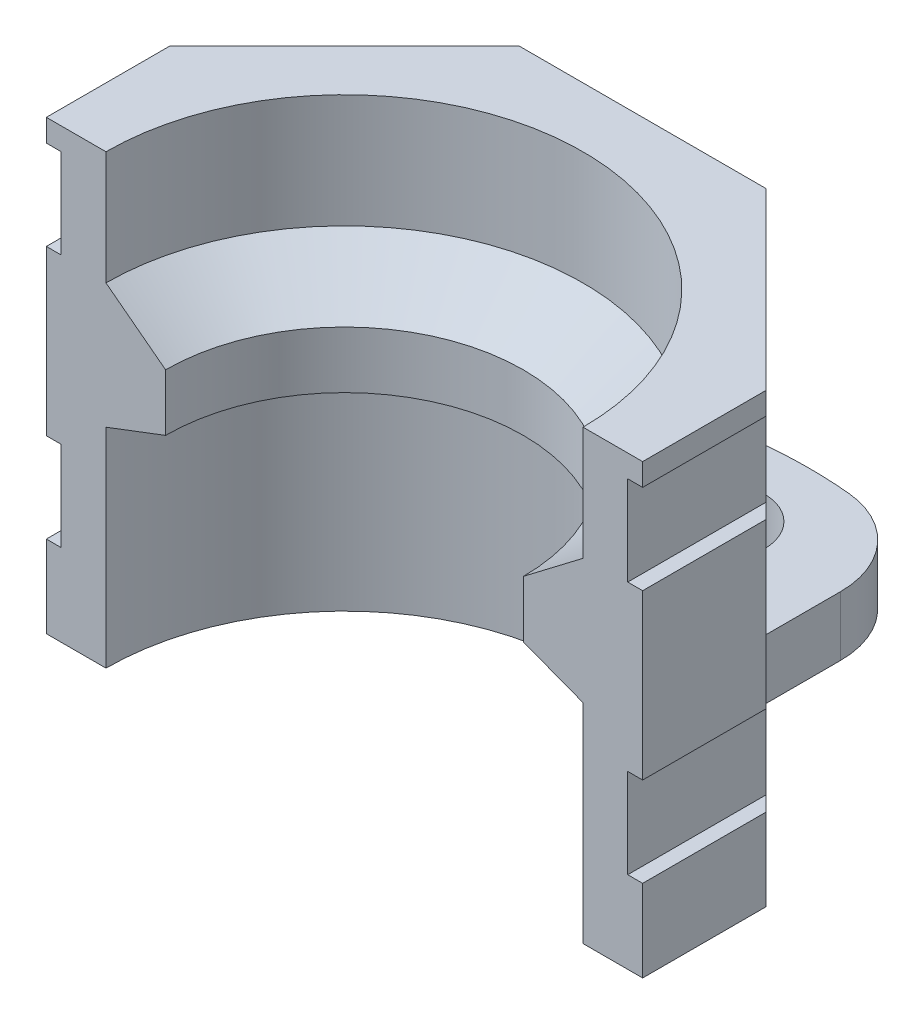
SolidWorks part; units mm, degrees
ref_plane "Front Plane" through (0, 0, 0) normal (0, 0, 1) x (1, 0, 0)
ref_plane "Top Plane" through (0, 0, 0) normal (0, 1, 0) x (1, 0, 0)
ref_plane "Right Plane" through (0, 0, 0) normal (1, 0, 0) x (0, 0, -1)
sketch "Sketch2" plane through (0, 0, 0) normal (0, 1, 0) x (1, 0, 0)
  line L0 (0, 10) -> (0, 0) construction
  line L1 (0, 0) -> (10, 0) construction
  line L2 (4.1421, 10) -> (-4.1421, 10)
  line L3 (-4.1421, 10) -> (-10, 4.1421)
  line L4 (-10, 4.1421) -> (-10, -4.1421)
  line L5 (4.1421, 10) -> (10, 4.1421)
  line L6 (10, 4.1421) -> (10, -4.1421)
  line L7 (4.1421, -10) -> (10, -4.1421)
  line L8 (4.1421, -10) -> (-4.1421, -10)
  line L9 (-4.1421, -10) -> (-10, -4.1421)
  point P9 (0, 10)
  point P12 (10, 0)
  point P15 (-10, 0)
  dimension "D1" = 20
extrude "Boss-Extrude1" add sketch "Sketch2" along normal blind 20
sketch "Sketch4" plane through (0, 0, 0) normal (0, 0, 1) x (1, 0, 0)
  line L0 (0, -24.1617) -> (0, 0) construction
  line L1 (-4.1421, 0) -> (4.1421, 0) construction
  line L2 (0, 0) -> (0, 20)
  line L4 (0, 20) -> (-4.625, 20)
  line L5 (-4.625, 20) -> (-4.375, 17)
  line L6 (-4.375, 17) -> (-1, 17)
  line L7 (-1, 17) -> (-1, 15)
  line L8 (-1, 15) -> (-8, 15)
  line L9 (-8, 15) -> (-8, 11.19)
  line L10 (-8, 11.19) -> (-6, 9.666)
  line L11 (-6, 9.666) -> (-6, 7.761)
  line L12 (-6, 7.761) -> (-8, 6.999)
  line L13 (-8, 6.999) -> (-8, 0)
  line L14 (-8, 0) -> (0, 0)
  line L15 (-4.1421, 20) -> (4.1421, 20) construction
  dimension "D1" = 2
  dimension "D2" = 9.25
  dimension "D3" = 8.75
  dimension "D4" = 3
  dimension "D5" = 3.81
  dimension "D6" = 1.524
  dimension "D7" = 16
  dimension "D8" = 12
  dimension "D9" = 4.191
  dimension "D10" = 1.905
  dimension "D11" = 2
revolve "Cut-Revolve3" cut sketch "Sketch4" angle 360 about L0
chamfer "Chamfer2" distance 3 angle 45 8 edges at (7.0711, 20, 7.0711) (0, 20, 10) (-7.0711, 20, 7.0711) (-10, 20, 0) (-7.0711, 20, -7.0711) (0, 20, -10) (7.0711, 20, -7.0711) (10, 20, 0)
sketch "Sketch7" plane through (0, 0, 0) normal (0, 0, 1) x (1, 0, 0)
  line L0 (-10, 8.5) -> (10, 8.5) construction
  line L1 (-10, 17) -> (-10, 0) construction
  line L2 (10, 17) -> (10, 0) construction
  line L3 (0, 0) -> (0, 17) construction
  line L4 (4.1421, 17) -> (-4.1421, 17) construction
  line L5 (-10, 2.75) -> (-9.5, 2.75)
  line L6 (-10, 14.25) -> (-9.5, 14.25)
  line L7 (-10, 14.25) -> (-10, 11.25)
  line L8 (-10, 11.25) -> (-9.5, 11.25)
  line L9 (-9.5, 14.25) -> (-9.5, 11.25)
  line L10 (-10, 2.75) -> (-10, 5.75)
  line L11 (-10, 5.75) -> (-9.5, 5.75)
  line L12 (-9.5, 2.75) -> (-9.5, 5.75)
  line L13 (10, 2.75) -> (9.5, 2.75)
  line L14 (9.5, 2.75) -> (9.5, 5.75)
  line L15 (10, 2.75) -> (10, 5.75)
  line L16 (10, 5.75) -> (9.5, 5.75)
  line L17 (10, 14.25) -> (9.5, 14.25)
  line L18 (10, 14.25) -> (10, 11.25)
  line L19 (10, 11.25) -> (9.5, 11.25)
  line L20 (9.5, 14.25) -> (9.5, 11.25)
  line L21 (-9.5, 11.25) -> (-9.5, 8.5) construction
  line L22 (-9.5, 17) -> (-9.5, 14.25) construction
  line L23 (-4.1421, 17) -> (-10, 17) construction
  dimension "D1" = 3
  dimension "D2" = 0.5
extrude "Cut-Extrude5" cut sketch "Sketch7" against normal through all both and the other way through all
sketch "Sketch8" plane through (0, 0, 0) normal (0, 1, 0) x (1, 0, 0)
  line L0 (0, 0) -> (10.8137, 6.27) construction
  line L1 (-4.1421, 10) -> (-4.1421, 12.5481)
  line L2 (-0.0231, 12.5) -> (-0.0231, 17.238) construction
  line L3 (-0.0231, 12.5) -> (-0.0231, 14.1) construction
  line L4 (-4.1421, 10) -> (0, 10)
  line L5 (-4.1421, 10) -> (4.1421, 10) construction
  line L6 (4.0959, 10) -> (4.0959, 12.5481)
  line L7 (4.0959, 10) -> (-0.0463, 10)
  line L8 (-4.1421, -10) -> (-10.1285, -10)
  line L9 (-12.6282, -8.6588) -> (-13.1321, -7.8995)
  line L10 (-12.379, -3.8017) -> (-11.2534, -2.9956)
  line L11 (-10, -0.5565) -> (-10, -4.1421)
  line L12 (-10, -4.1421) -> (-10, 4.1421) construction
  line L13 (-10, -4.1421) -> (-4.1421, -10)
  line L14 (9.9537, -4.1421) -> (4.0959, -10)
  line L15 (9.9537, -0.5565) -> (9.9537, -4.1421)
  line L16 (12.3327, -3.8017) -> (11.2071, -2.9956)
  line L17 (12.582, -8.6588) -> (13.0858, -7.8995)
  line L18 (4.0959, -10) -> (10.0823, -10)
  circle A0 centre (10.8137, 6.27) radius 1.6 construction
  circle A1 centre (10.8369, -6.23) radius 1.6
  circle A2 centre (0.0231, -12.5) radius 1.6 construction
  circle A3 centre (-10.8137, -6.27) radius 1.6
  circle A4 centre (-10.8369, 6.23) radius 1.6 construction
  circle A5 centre (-0.0231, 12.5) radius 1.6
  arc A6 (-1.4141, 15.5358) -> (-0.0231, 15.6) centre (0, 0) cw
  arc A7 (1.3678, 15.5358) -> (-0.0231, 15.6) centre (-0.0463, 0) ccw
  arc A8 (1.3678, 15.5358) -> (4.0959, 12.5481) centre (1.0959, 12.5481) cw
  arc A9 (-4.1421, 12.5481) -> (-1.4141, 15.5358) centre (-1.1421, 12.5481) cw
  arc A10 (-13.1321, -7.8995) -> (-12.379, -3.8017) centre (-10.6324, -6.2408) cw
  arc A11 (-10.1285, -10) -> (-12.6282, -8.6588) centre (-10.1285, -7) cw
  arc A12 (-11.2534, -2.9956) -> (-10, -0.5565) centre (-13, -0.5565) ccw
  arc A13 (11.2071, -2.9956) -> (9.9537, -0.5565) centre (12.9537, -0.5565) cw
  arc A14 (13.0858, -7.8995) -> (12.3327, -3.8017) centre (10.5861, -6.2408) ccw
  arc A15 (10.0823, -10) -> (12.582, -8.6588) centre (10.0823, -7) ccw
  point P29 (4.0959, 15.04)
  point P32 (-4.1421, 15.04)
  point P43 (-10, -2.0981)
  point P49 (-14.7328, -5.4872)
  point P52 (-11.7382, -10)
  dimension "D3" = 3.2
  dimension "D5" = 3
  dimension "D6" = 3
  dimension "D7" = 3
  dimension "D8" = 3
  dimension "D2" = 12.5
  dimension "D4" = 1.5
  dimension "D1" = 6
extrude "Boss-Extrude2" add sketch "Sketch8" along normal blind 2 contours A9 L1 L4 L7 L6 A8 A7 A6 A5 | A12 L10 A10 L9 A11 L8 L13 L11 A3 | L18 A15 L17 A14 L16 A13 L15 L14 A1 region at (-4.0425, 0, -11.2741) region at (-7.1353, 0, 9.8661) region at (9.6184, 0, 7.2772)
sketch "Sketch9" plane through (0, 0, 0) normal (0, 0, 1) x (1, 0, 0)
  line L1 (-7, 20) -> (-10, 17) construction
  line L5 (10, 17) -> (7, 20) construction
  line L10 (-8, 15) -> (8, 15) construction
  line L11 (-7, 20) -> (-10, 17)
  line L12 (10, 17) -> (7, 20)
  line L13 (-10, 15) -> (10, 15)
  line L14 (-10, 17) -> (-10, 15)
  line L15 (-10, 17) -> (-10, 14.25) construction
  line L16 (10, 17) -> (10, 15)
  line L17 (10, 17) -> (10, 14.25) construction
  line L18 (-7, 20) -> (7, 20)
extrude "Cut-Extrude6" cut sketch "Sketch9" against normal through all
sketch "Sketch10" plane through (0, 0, 0) normal (0, -1, 0) x (1, 0, 0)
  line L0 (0, 0) -> (-10, 0)
  line L1 (0, 0) -> (10, 0)
  line L2 (-10, -4.1421) -> (-10, 0.5565) construction
  line L4 (-12.379, 3.8017) -> (-11.2534, 2.9956) construction
  line L8 (-12.6282, 8.6588) -> (-13.1321, 7.8995) construction
  line L14 (-10.1285, 10) -> (10.0823, 10) construction
  line L22 (12.582, 8.6588) -> (13.0858, 7.8995) construction
  line L32 (12.3327, 3.8017) -> (11.2071, 2.9956) construction
  line L44 (10, 1.0814) -> (10, -4.1421) construction
  line L58 (-10, 0) -> (-10, 0.5565)
  line L59 (-12.379, 3.8017) -> (-11.2534, 2.9956)
  line L60 (-12.6282, 8.6588) -> (-13.1321, 7.8995)
  line L61 (-10.1285, 10) -> (10.0823, 10)
  line L62 (12.582, 8.6588) -> (13.0858, 7.8995)
  line L63 (12.3327, 3.8017) -> (11.2071, 2.9956)
  line L64 (10, 1.0814) -> (10, 0)
  arc A0 (-10, 0.5565) -> (-11.2534, 2.9956) centre (-13, 0.5565) ccw construction
  arc A2 (-13.1321, 7.8995) -> (-12.379, 3.8017) centre (-10.6324, 6.2408) ccw construction
  arc A6 (-10.1285, 10) -> (-12.6282, 8.6588) centre (-10.1285, 7) ccw construction
  arc A12 (12.582, 8.6588) -> (10.0823, 10) centre (10.0823, 7) ccw construction
  arc A20 (12.3327, 3.8017) -> (13.0858, 7.8995) centre (10.5861, 6.2408) ccw construction
  arc A30 (11.2071, 2.9956) -> (10, 1.0814) centre (12.9537, 0.5565) ccw construction
  arc A48 (-10, 0.5565) -> (-11.2534, 2.9956) centre (-13, 0.5565) ccw
  arc A49 (-13.1321, 7.8995) -> (-12.379, 3.8017) centre (-10.6324, 6.2408) ccw
  arc A50 (-10.1285, 10) -> (-12.6282, 8.6588) centre (-10.1285, 7) ccw
  arc A51 (12.582, 8.6588) -> (10.0823, 10) centre (10.0823, 7) ccw
  arc A52 (12.3327, 3.8017) -> (13.0858, 7.8995) centre (10.5861, 6.2408) ccw
  arc A53 (11.2071, 2.9956) -> (10, 1.0814) centre (12.9537, 0.5565) ccw
extrude "Cut-Extrude7" cut sketch "Sketch10" against normal through all
sketch "Sketch11" [suppressed] plane through (0, 0, 0) normal (0, 0, 1) x (1, 0, 0)
  line L0 (-8, 15) -> (8, 15) construction
  line L1 (-10, 15) -> (10, 15)
  line L2 (10, 17) -> (10, 14.25) construction
  line L3 (-10, 17) -> (-10, 14.25) construction
  line L4 (10, 15) -> (10, 0)
  line L5 (10, 0) -> (-10, 0)
  line L6 (-10, 0) -> (-10, 15)
extrude "Cut-Extrude8" [suppressed] cut sketch "Sketch11" against normal through all
